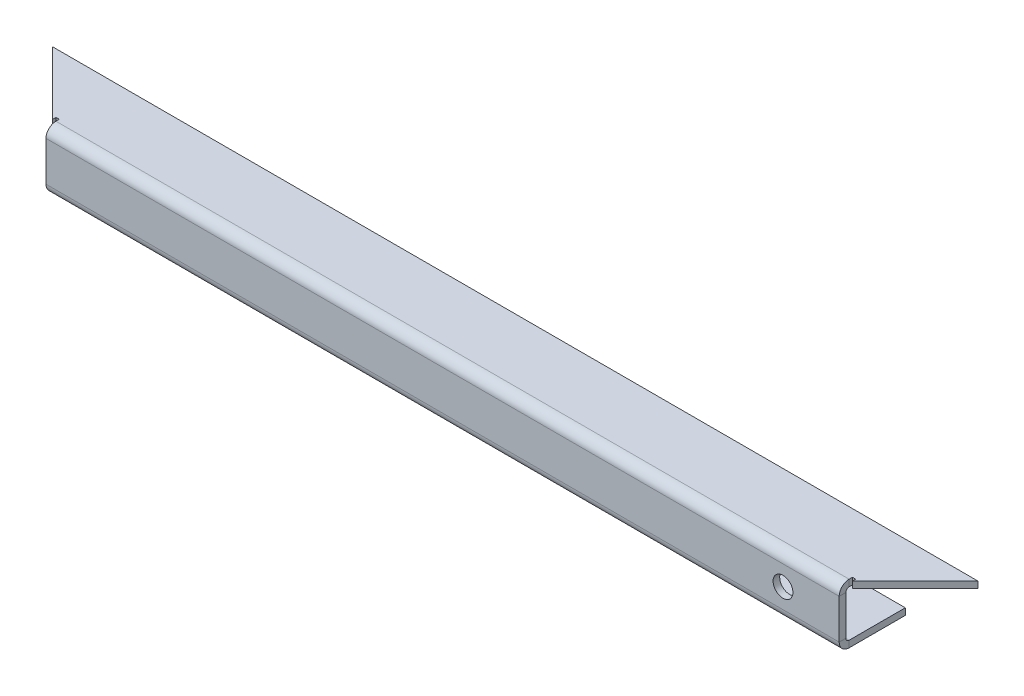
SolidWorks part; units mm, degrees
note: The reader was unsure of these and kept them because the rebuilt part matched: flange length of "Edge-Flange1", "Edge-Flange2".
material "St.37"
ref_plane "Front Plane" through (0, 0, 0) normal (0, 0, 1) x (1, 0, 0)
ref_plane "Top Plane" through (0, 0, 0) normal (0, 1, 0) x (1, 0, 0)
ref_plane "Right Plane" through (0, 0, 0) normal (1, 0, 0) x (0, 0, -1)
sketch "Sketch1" plane through (0, 0, 0) normal (0, 1, 0) x (1, 0, 0)
  line L0 (-60, 0) -> (60, 0)
  line L1 (-60, 0) -> (-70, 10)
  line L2 (60, 0) -> (70, 10)
  line L3 (-70, 10) -> (70, 10)
  point P3 (0, 0)
  dimension "D1" = 120
  dimension "D2" = 135
  dimension "D3" = 10
base flange "Base-Flange1" sketch "Sketch1" thickness 1 reverse thickness direction no parameters "D1"=1
edge flange "Edge-Flange1" sketch "Sketch8" flange angle 90 flange length 8 flange position material outside bend radius 0.5 thickness 1 relief rectangular parameters "D6"=10
sketch "Sketch8" plane through (0, -1, 0) normal (0, 0, 1) x (-1, 0, 0)
  line L2 (-60, 0) -> (-60, 7)
  line L3 (-60, 7) -> (60, 7)
  line L4 (60, 7) -> (60, 0)
  line L7 (60, 0) -> (-60, 0) construction
  line L8 (60, 0) -> (-60, 0)
bend "EdgeBend1" bend radius 0.5 bend angle 90 parameters "D5"=1
edge flange "Edge-Flange2" sketch "Sketch11" flange angle 90 flange length 10 flange position material outside bend radius 0.5 thickness 1 relief rectangular parameters "D6"=10
sketch "Sketch11" plane through (0, -8, 0) normal (0, -1, 0) x (-1, 0, 0)
  line L2 (-60, 0) -> (-60, 9)
  line L3 (-60, 9) -> (60, 9)
  line L4 (60, 9) -> (60, 0)
  line L7 (60, 0) -> (-60, 0) construction
  line L8 (60, 0) -> (-60, 0)
bend "EdgeBend2" bend radius 0.5 bend angle 90 parameters "D5"=2
sketch "Sketch12" plane through (0, -9, 0) normal (0, -1, 0) x (1, 0, 0)
  line L0 (-60, -0.5) -> (-60, -9) construction
  line L1 (-60, -9) -> (60, -9) construction
  line L2 (60, -9) -> (60, -0.5) construction
  circle A0 centre (-50, -5) radius 1.5
  circle A1 centre (0, -5) radius 1.5
  circle A2 centre (50, -5) radius 1.5
  dimension "D2" = 3
  dimension "D1" = 10
  dimension "D3" = 4
  dimension "D5" = 10
  dimension "D4" = 3
extrude "Cut-Extrude1" cut sketch "Sketch12" against normal blind 3 normal cut yes
sketch "Sketch13" plane through (0, 0, 0) normal (0, 0, -1) x (-1, 0, 0)
  line L0 (-60, -7.5) -> (-60, -1.5) construction
  line L1 (-70, -1) -> (70, -1) construction
  circle A0 centre (-51.5, -4.5) radius 1.5
  dimension "D2" = 3
  dimension "D1" = 8.5
  dimension "D3" = 3.5
extrude "Cut-Extrude2" cut sketch "Sketch13" against normal blind 3 normal cut yes
sketch "Bend-Lines1" [suppressed] plane through (0, 0, 0) normal (0, 1, 0) x (1, 0, 0)
sketch "Bounding-Box1" [suppressed] plane through (0, 0, 0) normal (0, 1, 0) x (1, 0, 0)
sheet metal parameters "Sheet-Metal1" thickness 1 parameters "D1"=1
flat pattern "Flat-Pattern1" [suppressed]
sketch "Bend-Lines2" plane through (0, 0, 0) normal (0, 1, 0) x (1, 0, 0)
sketch3d "Bounding-Box2" [suppressed]
  line L0 (-70, 10, 0) -> (70, 10, 0) construction
  line L1 (-70, 0, 0) -> (70, 0, 0) construction
  line L2 (-70, 10, 0) -> (-70, 0, 0) construction
  line L3 (70, 10, 0) -> (70, 0, 0) construction
sheet metal parameters "Sheet-Metal2" thickness 1 parameters "D1"=1
flat pattern "Flat-Pattern1"
sketch "Bend-Lines2" plane through (0, 0, 0) normal (0, 1, 0) x (1, 0, 0)
  line L0 (-60, -0.2854) -> (60, -0.2854) construction
  line L1 (-60, -0.2854) -> (60, -0.2854) construction
sketch3d "Bounding-Box2" [suppressed]
  line L0 (70, 10, 0) -> (-70, 10, 0) construction
  line L1 (70, -7.5708, 0) -> (-70, -7.5708, 0) construction
  line L2 (70, 10, 0) -> (70, -7.5708, 0) construction
  line L3 (-70, 10, 0) -> (-70, -7.5708, 0) construction
bend of the flat pattern "Flatten-<EdgeBend1>1"
sheet metal parameters "Sheet-Metal3" thickness 1 parameters "D1"=1
flat pattern "Flat-Pattern1"
sketch "Bend-Lines2" plane through (0, 0, 0) normal (0, 1, 0) x (1, 0, 0)
  line L0 (-60, -0.2854) -> (60, -0.2854) construction
  line L1 (-60, -0.2854) -> (60, -0.2854) construction
  line L2 (-60, -7.7489) -> (60, -7.7489) construction
  line L3 (-60, -7.7489) -> (60, -7.7489) construction
sketch3d "Bounding-Box2" [suppressed]
  line L0 (70, 10, 0) -> (-70, 10, 0) construction
  line L1 (70, -16.927, 0) -> (-70, -16.927, 0) construction
  line L2 (70, 10, 0) -> (70, -16.927, 0) construction
  line L3 (-70, 10, 0) -> (-70, -16.927, 0) construction
bend of the flat pattern "Flatten-<EdgeBend1>1"
bend of the flat pattern "Flatten-<EdgeBend2>1"
sheet metal parameters "Sheet-Metal4" thickness 1 parameters "D1"=1
flat pattern "Flat-Pattern1"
sketch "Bend-Lines2" plane through (0, 0, 0) normal (0, 1, 0) x (1, 0, 0)
  line L0 (-60, -0.2854) -> (60, -0.2854) construction
  line L1 (-60, -0.2854) -> (60, -0.2854) construction
  line L2 (-60, -7.8562) -> (60, -7.8562) construction
  line L3 (-60, -7.8562) -> (60, -7.8562) construction
sketch3d "Bounding-Box2" [suppressed]
  line L0 (70, 10, 0) -> (-70, 10, 0) construction
  line L1 (70, -17.1416, 0) -> (-70, -17.1416, 0) construction
  line L2 (70, 10, 0) -> (70, -17.1416, 0) construction
  line L3 (-70, 10, 0) -> (-70, -17.1416, 0) construction
bend of the flat pattern "Flatten-<EdgeBend1>1"
bend of the flat pattern "Flatten-<EdgeBend2>1"
sheet metal parameters "Sheet-Metal5" thickness 1 parameters "D1"=1
flat pattern "Flat-Pattern1"
sketch "Bend-Lines2" plane through (0, 0, 0) normal (0, 1, 0) x (1, 0, 0)
  line L0 (-60, -0.2854) -> (60, -0.2854) construction
  line L1 (-60, -0.2854) -> (60, -0.2854) construction
  line L2 (-60, -7.8562) -> (60, -7.8562) construction
  line L3 (-60, -7.8562) -> (60, -7.8562) construction
sketch3d "Bounding-Box2" [suppressed]
  line L0 (70, 10, 0) -> (-70, 10, 0) construction
  line L1 (70, -17.1416, 0) -> (-70, -17.1416, 0) construction
  line L2 (70, 10, 0) -> (70, -17.1416, 0) construction
  line L3 (-70, 10, 0) -> (-70, -17.1416, 0) construction
bend of the flat pattern "Flatten-<EdgeBend1>1"
bend of the flat pattern "Flatten-<EdgeBend2>1"
